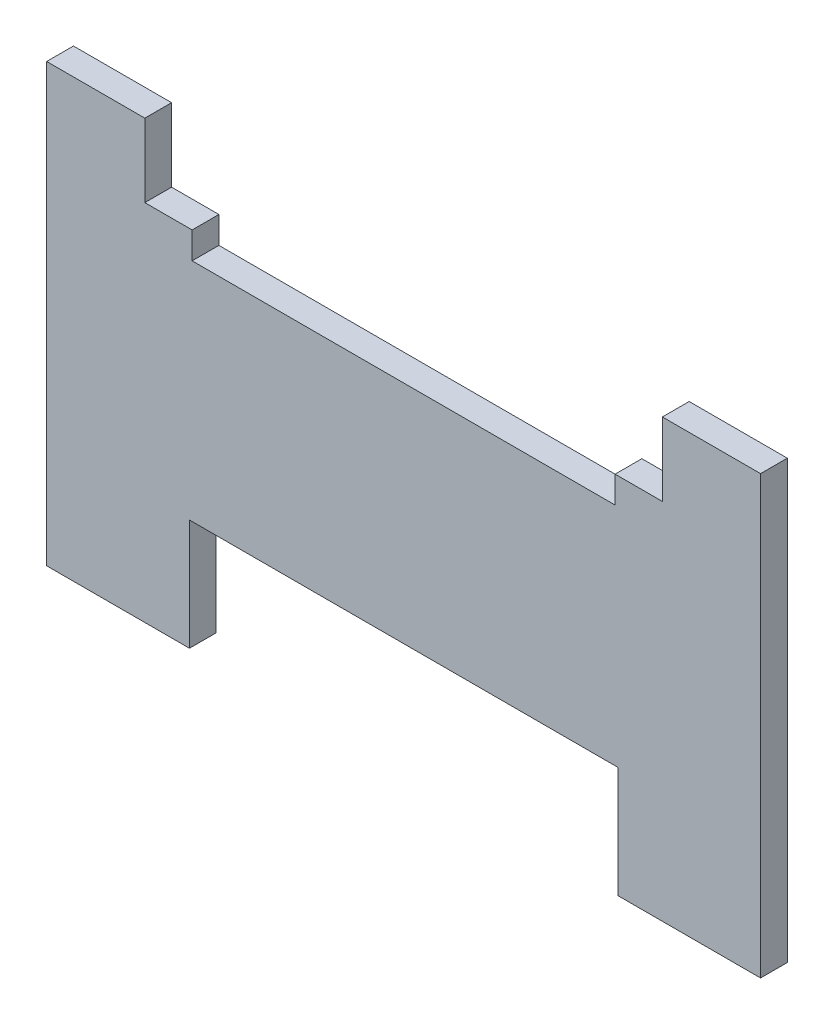
SolidWorks part; units mm, degrees
ref_plane "Front Plane" through (0, 0, 0) normal (0, 0, 1) x (1, 0, 0)
ref_plane "Top Plane" through (0, 0, 0) normal (0, 1, 0) x (1, 0, 0)
ref_plane "Right Plane" through (0, 0, 0) normal (1, 0, 0) x (0, 0, -1)
sketch "Sketch1" plane through (0, 0, 0) normal (0, 0, 1) x (1, 0, 0)
  line L0 (0, 52.125) -> (11, 52.125)
  line L1 (80, 52.125) -> (80, 3.175)
  line L2 (80, 3.175) -> (64, 3.175)
  line L3 (64, 3.175) -> (64, 15.625)
  line L4 (64, 15.625) -> (16, 15.625)
  line L5 (16, 15.625) -> (16, 3.175)
  line L6 (16, 3.175) -> (0, 3.175)
  line L7 (0, 3.175) -> (0, 52.125)
  line L8 (16, 3.175) -> (0, 3.175) construction
  line L9 (0, 15.625) -> (80, 15.625) construction
  line L10 (16, 18.625) -> (16, 3.175) construction
  line L11 (64, 18.625) -> (64, 3.175) construction
  line L12 (80, 3.175) -> (80, 52.125) construction
  line L13 (0, 3.175) -> (0, 52.125) construction
  line L15 (40, 15.625) -> (40, 52.125) construction
  line L16 (40, 0) -> (40, 67.125) construction
  line L17 (3, 49.125) -> (3, 6.175) construction
  line L18 (3, 6.175) -> (16, 6.175) construction
  line L19 (64, 6.175) -> (77, 6.175) construction
  line L20 (77, 6.175) -> (77, 49.125) construction
  line L21 (77, 49.125) -> (3, 49.125) construction
  line L22 (0, 18.625) -> (80, 18.625) construction
  line L23 (64, 15.625) -> (80, 15.625) construction
  line L24 (16, 15.625) -> (0, 15.625) construction
  line L25 (8, 3.175) -> (8, 6.175) construction
  line L26 (72, 3.175) -> (72, 6.175) construction
  line L27 (77, 6.175) -> (77, 49.125) construction
  line L28 (77, 6.175) -> (64, 6.175) construction
  line L29 (72, 3.175) -> (72, 6.175) construction
  line L30 (16, 6.175) -> (3, 6.175) construction
  line L31 (3, 6.175) -> (3, 49.125) construction
  line L32 (8, 3.175) -> (8, 6.175) construction
  line L33 (80, 18.625) -> (0, 18.625) construction
  line L34 (77, 49.125) -> (3, 49.125) construction
  line L35 (45.3, 50.175) -> (45.3, 8.175) construction
  line L36 (45.3, 8.175) -> (42.3, 8.175) construction
  line L37 (42.3, 50.175) -> (42.3, 8.175) construction
  line L38 (45.3, 50.175) -> (42.3, 50.175) construction
  line L39 (45.3, 50.175) -> (45.3, 8.175) construction
  line L40 (45.3, 8.175) -> (42.3, 8.175) construction
  line L41 (42.3, 50.175) -> (42.3, 8.175) construction
  line L42 (45.3, 50.175) -> (42.3, 50.175) construction
  line L43 (72, 40.925) -> (72, 52.125) construction
  line L44 (0, 52.125) -> (80, 52.125) construction
  line L45 (8, 52.125) -> (8, 40.925) construction
  line L46 (8, 40.925) -> (72, 40.925) construction
  line L47 (72, 52.125) -> (72, 40.925) construction
  line L48 (8, 40.925) -> (8, 52.125) construction
  line L49 (16.3, 40.925) -> (8, 40.925) construction
  line L50 (8, 52.125) -> (16.3, 52.125) construction
  line L51 (11, 49.125) -> (11, 43.925) construction
  line L53 (11, 52.125) -> (11, 43.925)
  line L54 (11, 43.925) -> (69, 43.925) construction
  line L55 (69, 52.125) -> (69, 43.925)
  line L56 (69, 52.125) -> (80, 52.125)
  line L57 (69, 49.125) -> (69, 43.925) construction
  line L59 (69, 43.925) -> (63.7, 43.925) construction
  line L60 (16.3, 52.125) -> (16.3, 49.125) construction
  line L61 (16.3, 43.925) -> (16.3, 40.925)
  line L62 (16.3, 52.125) -> (16.3, 49.125) construction
  line L63 (63.7, 52.125) -> (63.7, 49.125) construction
  line L64 (63.7, 43.925) -> (63.7, 40.925)
  line L65 (63.7, 52.125) -> (63.7, 49.125) construction
  line L66 (48.3, 53.175) -> (48.3, 5.175) construction
  line L67 (48.3, 5.175) -> (39.3, 5.175) construction
  line L70 (39.3, 53.175) -> (39.3, 5.175) construction
  line L71 (48.3, 53.175) -> (39.3, 53.175) construction
  line L72 (63.7, 43.925) -> (69, 43.925)
  line L73 (11, 43.925) -> (16.3, 43.925)
  line L74 (39.3, 53.175) -> (39.3, 44.225) construction
  line L80 (16.3, 40.925) -> (63.7, 40.925)
sketch "Sketch2" plane through (0, 0, 0) normal (1, 0, 0) x (0, 0, -1)
  line L1 (0, 52.125) -> (3, 52.125)
  line L2 (0, 52.125) -> (0, 3.175)
  line L3 (0, 3.175) -> (3, 3.175)
  line L4 (3, 52.125) -> (3, 3.175)
extrude "Boss-Extrude1" add sketch "Sketch1" against normal up to vertex (3 mm away) up to point (0, 52.125, -3)
